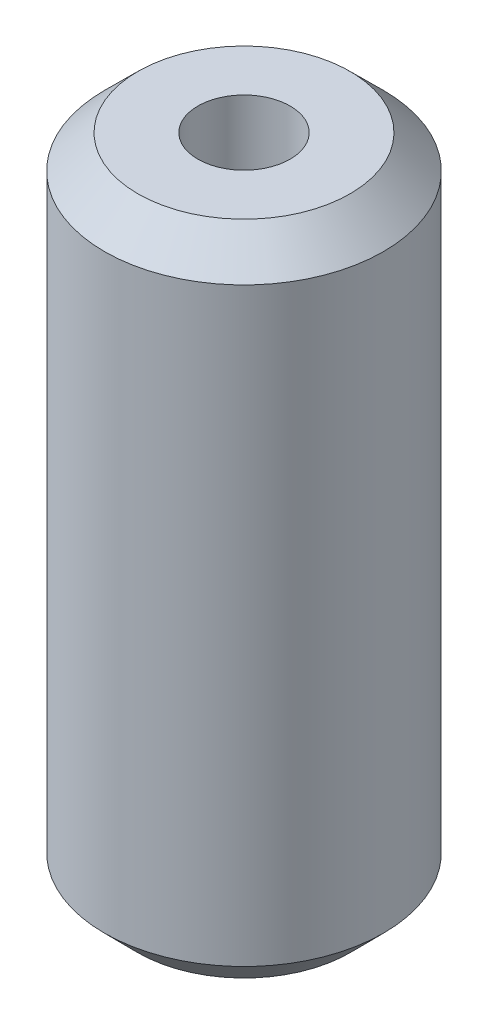
SolidWorks part; units mm, degrees
ref_plane "Front Plane" through (0, 0, 0) normal (0, 0, 1) x (1, 0, 0)
ref_plane "Top Plane" through (0, 0, 0) normal (0, 1, 0) x (1, 0, 0)
ref_plane "Right Plane" through (0, 0, 0) normal (1, 0, 0) x (0, 0, -1)
sketch "Sketch1" plane through (0, 0, 0) normal (0, 1, 0) x (1, 0, 0)
  circle A0 centre (0, 0) radius 5
  dimension "SHAFT_OD" = 10
extrude "Boss-Extrude1" add sketch "Sketch1" along normal blind 23.5379
sketch "Sketch2" plane through (0, 0, 0) normal (0, 1, 0) x (1, 0, 0)
  circle A0 centre (0, 0) radius 1.652
  dimension "BORE_D" = 3.304
extrude "Cut-Extrude1" cut sketch "Sketch2" along normal through all
chamfer "Chamfer1" distance 1.1913 angle 45.211 2 edges at (0, 23.5379, 5) (0, 0, 5) first distance on face at (0, 23.5379, 5) first distance on face at (0, 0, 1.652)
